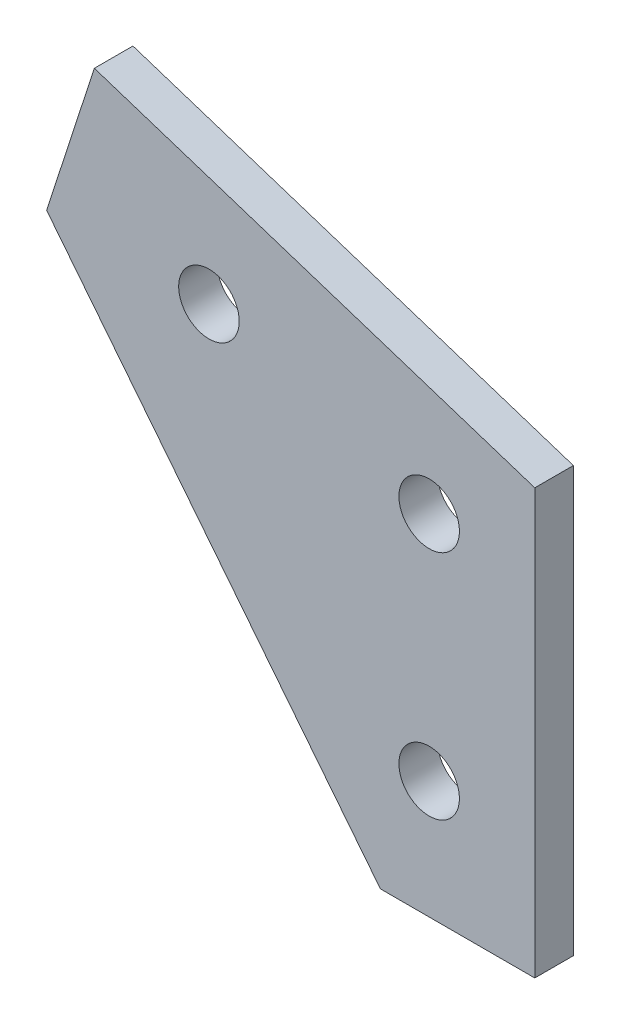
SolidWorks part; units mm, degrees
ref_plane "Front Plane" through (0, 0, 0) normal (0, 0, 1) x (1, 0, 0)
ref_plane "Top Plane" through (0, 0, 0) normal (0, 1, 0) x (1, 0, 0)
ref_plane "Right Plane" through (0, 0, 0) normal (1, 0, 0) x (0, 0, -1)
sketch "Sketch4" plane through (0, 0, 0) normal (0, 0, 1) x (1, 0, 0)
  line L0 (-40.992, 298.8407) -> (-42.9542, 292.8015) construction
  line L1 (-40.992, 298.8407) -> (-53.3542, 260.7936) construction
  line L2 (-42.9542, 292.8015) -> (-6.719, 281.0279)
  line L3 (-42.9542, 292.8015) -> (-46.8787, 280.723)
  line L4 (-6.719, 281.0279) -> (-6.719, 246.1029)
  line L5 (-6.719, 246.1029) -> (-19.419, 246.1029)
  line L6 (-19.419, 246.1029) -> (-46.8787, 280.723)
extrude "Boss-Extrude1" add sketch "Sketch4" along normal blind 3.175
hole_wizard "#10 Clearance Hole1" positions "Sketch5" profile "Sketch6" hole size "#10" standard "ANSI Inch" end condition through all
sketch "Sketch5" plane through (0, 0, 3.175) normal (0, 0, 1) x (1, 0, 0)
  point P0 (-33.5252, 280.723)
  point P3 (-15.4075, 274.8363)
  point P6 (-15.4075, 255.7863)
sketch "Sketch6" plane through (-33.5252, 280.723, 3.175) normal (1, 0, 0) x (0, -1, 0)
  line L0 (0, 0) -> (0, 3.175)
  line L1 (0, 3.175) -> (2.4892, 3.175)
  line L2 (2.4892, 3.175) -> (2.4892, 0)
  line L5 (2.4892, 0) -> (0, 0)
  line L11 (0, -6.35) -> (0, 107.95) construction
  dimension "Thru Hole Dia." = 4.9784
  dimension "Thru Hole Depth" = 3.175
